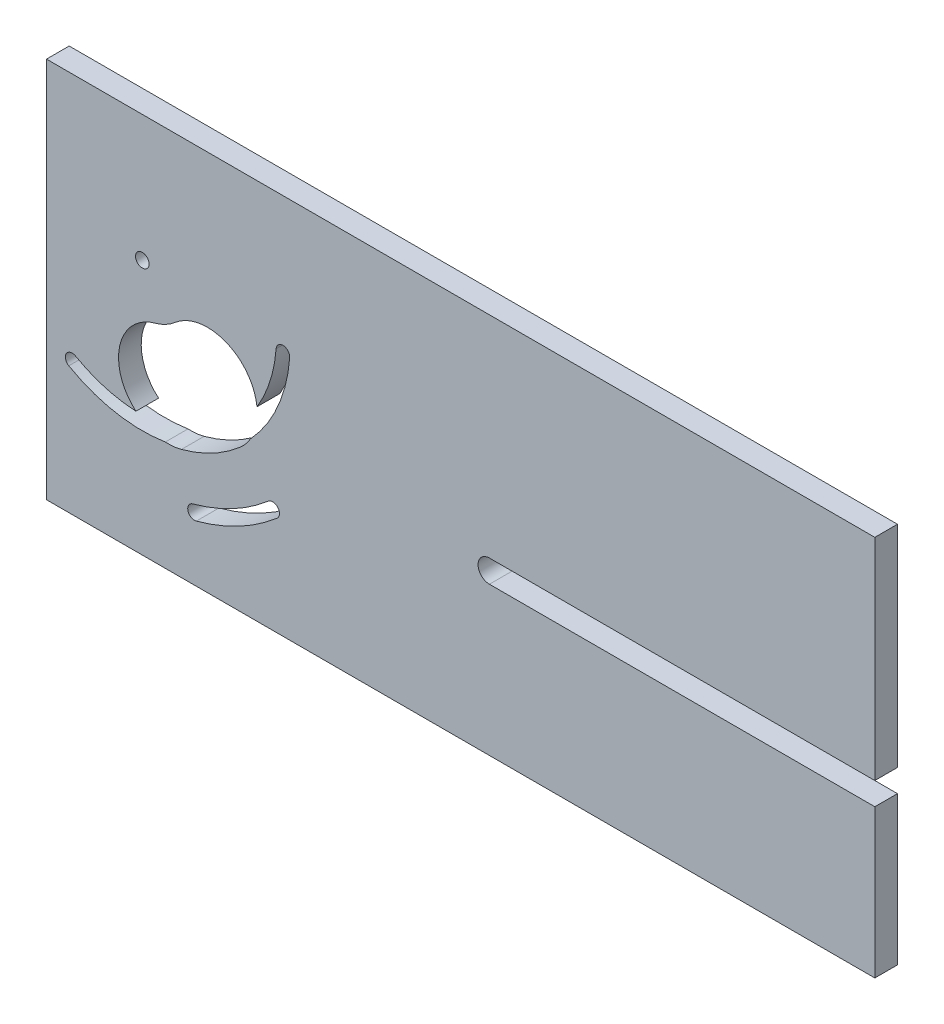
SolidWorks part; units mm, degrees
ref_plane "Front" through (0, 0, 0) normal (0, 0, 1) x (1, 0, 0)
ref_plane "Top" through (0, 0, 0) normal (0, 1, 0) x (1, 0, 0)
ref_plane "Right" through (0, 0, 0) normal (1, 0, 0) x (0, 0, -1)
sketch "Sketch1" plane through (0, 0, 0) normal (0, 0, 1) x (1, 0, 0)
  line L0 (-70.2236, 14.2507) -> (-39.2061, 11.9862) construction
  line L1 (-91.35, -42.09) -> (91.35, -42.09)
  line L2 (-91.35, -42.09) -> (-91.35, 42.09)
  line L3 (-91.35, 42.09) -> (91.35, 42.09)
  line L4 (91.35, -42.09) -> (91.35, 42.09)
  line L5 (-91.35, -42.09) -> (91.35, 42.09) construction
  line L6 (-91.35, 42.09) -> (91.35, -42.09) construction
  line L7 (-75.8236, -22.4493) -> (-33.5236, -22.4493) construction
  line L8 (-75.8236, -22.4493) -> (-75.8236, 19.8507) construction
  line L9 (-75.8236, 19.8507) -> (-33.5236, 19.8507) construction
  line L10 (-33.5236, -22.4493) -> (-33.5236, 19.8507) construction
  line L11 (-75.8236, -22.4493) -> (-33.5236, 19.8507) construction
  line L12 (-75.8236, 19.8507) -> (-33.5236, -22.4493) construction
  line L13 (-70.2236, -16.8493) -> (-39.1236, -16.8493) construction
  line L14 (-70.2236, -16.8493) -> (-70.2236, 14.2507) construction
  line L15 (-70.2236, 14.2507) -> (-39.1236, 14.2507) construction
  line L16 (-39.1236, -16.8493) -> (-39.1236, 14.2507) construction
  line L17 (-70.2236, -16.8493) -> (-39.1236, 14.2507) construction
  line L18 (-70.2236, 14.2507) -> (-39.1236, -16.8493) construction
  line L19 (-70.2236, 14.2507) -> (-85.6857, -12.7332) construction
  line L20 (-70.2236, 14.2507) -> (-58.7018, -28.1954) construction
  line L21 (-70.2236, 14.2507) -> (-41.4706, -19.0312) construction
  line L22 (-81.35, 48.3317) -> (101.35, 48.3317) construction
  line L23 (6.3431, -4.3738) -> (91.35, -4.3738)
  line L24 (6.3431, -9.3738) -> (91.35, -9.3738)
  arc A0 (6.3431, -4.3738) -> (6.3431, -9.3738) centre (6.3431, -6.8738) ccw
  circle A1 centre (-39.1236, 14.2507) radius 1.5 construction
  circle A2 centre (-70.2236, 14.2507) radius 1.5
  circle A3 centre (-70.2236, -16.8493) radius 1.5 construction
  circle A4 centre (-39.1236, -16.8493) radius 1.5 construction
  circle A5 centre (-70.2236, 14.2507) radius 31.1 construction
  circle A6 centre (-70.2236, 14.2507) radius 43.982 construction
  arc A7 (-86.4315, -14.0347) -> (-65.1444, -17.9512) centre (-70.2236, 14.2507) ccw
  arc A8 (-58.3088, -29.643) -> (-40.49, -20.1663) centre (-70.2236, 14.2507) ccw
  arc A9 (-84.9399, -11.4318) -> (-71.6311, -15.3158) centre (-70.2236, 14.2507) ccw
  arc A10 (-59.0947, -26.7478) -> (-42.4512, -17.8962) centre (-70.2236, 14.2507) ccw
  circle A11 centre (-39.2061, 11.9862) radius 1.5
  circle A12 centre (-41.4706, -19.0312) radius 1.5
  circle A13 centre (-85.6857, -12.7332) radius 1.5
  circle A14 centre (-58.7018, -28.1954) radius 1.5
  circle A15 centre (-70.2236, 14.2507) radius 29.6 construction
  circle A16 centre (-70.2236, 14.2507) radius 32.6 construction
  circle A17 centre (-70.2236, 14.2507) radius 42.482 construction
  circle A18 centre (-70.2236, 14.2507) radius 45.482 construction
  circle A19 centre (6.3431, -6.8738) radius 2.5 construction
  circle A20 centre (-70.2236, 14.2507) radius 21.991 construction
  arc A21 (-63.0383, 5.9336) -> (-44.9217, -1.1109) centre (-55.8471, -2.3903) cw
  arc A22 (-67.3443, 3.6435) -> (-71.6311, -15.3158) centre (-64.4627, -6.9723) ccw
  arc A23 (-67.3443, 3.6435) -> (-63.0383, 5.9336) centre (-70.2236, 14.2507) ccw
  arc A24 (-44.9217, -1.1109) -> (-40.7021, 12.0954) centre (-70.2236, 14.2507) ccw
  arc A25 (-61.581, -17.5882) -> (-48.6559, -10.7141) centre (-70.2236, 14.2507) ccw
  arc A26 (-46.3629, -7.9626) -> (-37.7101, 11.877) centre (-70.2236, 14.2507) ccw
  arc A27 (-46.3629, -7.9626) -> (-48.6559, -10.7141) centre (-55.8471, -2.3903) cw
  arc A28 (-65.1444, -17.9512) -> (-61.581, -17.5882) centre (-64.4627, -6.9723) ccw
  point P0 (0, 0)
  point P8 (-54.6736, -1.2993)
  point P13 (-54.6736, -1.2993)
  dimension "D2" = 3
  dimension "D8" = 11
  dimension "D1" = 31.1
  dimension "D3" = 42.3
  dimension "D6" = 45
  dimension "D7" = 45
  dimension "D9" = 84.18
  dimension "D4" = 1.5
  dimension "D5" = 1.5
extrude "Boss-Extrude1" add sketch "Sketch1" along normal blind 5 contours L1 L4 L3 L2 A14 A10 A12 A8 A0 A13 A9 A11 A7 region at (1.7975, 0.5635, 0)
